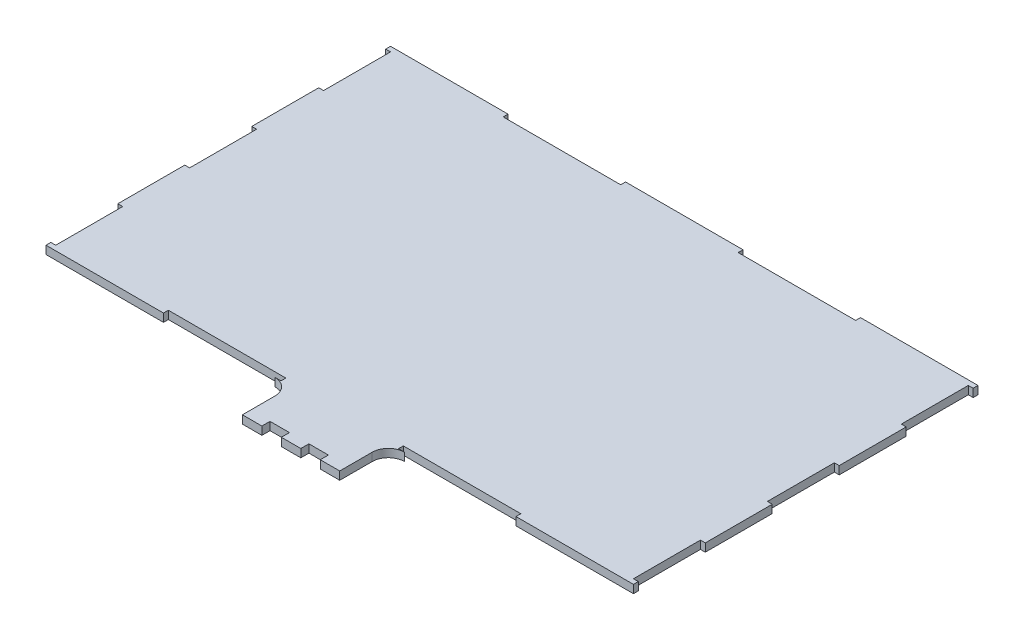
SolidWorks part; units mm, degrees
ref_plane "Front Plane" through (0, 0, 0) normal (0, 0, 1) x (1, 0, 0)
ref_plane "Top Plane" through (0, 0, 0) normal (0, 1, 0) x (1, 0, 0)
ref_plane "Right Plane" through (0, 0, 0) normal (1, 0, 0) x (0, 0, -1)
sketch "Sketch1" plane through (0, 0, 0) normal (0, 1, 0) x (1, 0, 0)
  line L0 (-30, -136.2503) -> (-18, -136.2503)
  line L5 (-181.15, 106.25) -> (181.15, -106.25) construction
  line L6 (-181.15, -106.25) -> (181.15, 106.25) construction
  line L13 (-30, -116.25) -> (-30, -136.2503)
  line L17 (30, -136.2503) -> (30, -116.25)
  line L18 (-18, -131.2503) -> (-6, -131.2503)
  line L20 (18, -136.2503) -> (30, -136.2503)
  line L21 (-6, -136.2503) -> (6, -136.2503)
  line L23 (-18, -136.2503) -> (-18, -131.2503)
  line L24 (-6, -136.2503) -> (-6, -131.2503)
  line L25 (6, -136.2503) -> (6, -131.2503)
  line L26 (18, -136.2503) -> (18, -131.2503)
  line L28 (6, -131.2503) -> (18, -131.2503)
  line L54 (-181.15, 106.25) -> (-181.15, 103.25) construction
  line L55 (181.15, 106.25) -> (108.69, 106.25)
  line L60 (-181.15, -106.25) -> (-181.15, -103.25)
  line L62 (-181.15, 103.25) -> (181.15, 103.25) construction
  line L63 (-108.69, 103.2497) -> (-36.23, 103.2497)
  line L64 (36.23, 106.25) -> (-36.23, 106.25)
  line L65 (36.23, 103.2497) -> (108.69, 103.2497)
  line L66 (-108.69, 103.2497) -> (-108.69, 106.25)
  line L67 (-36.23, 103.2497) -> (-36.23, 106.25)
  line L68 (36.23, 103.2497) -> (36.23, 106.25)
  line L69 (108.69, 103.2497) -> (108.69, 106.25)
  line L70 (-108.69, 106.25) -> (-181.15, 106.25)
  line L71 (-181.15, -103.25) -> (-178.15, -103.25)
  line L72 (-181.15, -103.25) -> (181.15, -103.25) construction
  line L73 (-178.15, -103.25) -> (-178.15, -61.95)
  line L74 (-181.15, -61.95) -> (-181.15, -20.65)
  line L75 (-178.15, -20.65) -> (-178.15, 20.65)
  line L76 (-181.15, 20.65) -> (-181.15, 61.95)
  line L77 (-178.15, 61.95) -> (-178.15, 103.25)
  line L78 (-178.15, 61.95) -> (-181.15, 61.95)
  line L79 (-178.15, 20.65) -> (-181.15, 20.65)
  line L80 (-178.15, -20.65) -> (-181.15, -20.65)
  line L81 (-178.15, -61.95) -> (-181.15, -61.95)
  line L82 (-181.15, 103.25) -> (-181.15, 106.25)
  line L83 (-181.15, 103.25) -> (-178.15, 103.25)
  line L84 (-36.23, -106.25) -> (-40, -106.25)
  line L85 (181.15, -103.25) -> (178.15, -103.25)
  line L86 (178.15, -103.25) -> (178.15, -61.95)
  line L87 (178.15, -61.95) -> (181.15, -61.95)
  line L88 (181.15, -61.95) -> (181.15, -20.65)
  line L89 (178.15, -20.65) -> (181.15, -20.65)
  line L90 (178.15, -20.65) -> (178.15, 20.65)
  line L91 (178.15, 20.65) -> (181.15, 20.65)
  line L92 (181.15, 20.65) -> (181.15, 61.95)
  line L93 (178.15, 61.95) -> (181.15, 61.95)
  line L94 (178.15, 61.95) -> (178.15, 103.25)
  line L95 (181.15, 103.25) -> (178.15, 103.25)
  line L96 (181.15, -106.25) -> (181.15, -103.25)
  line L97 (181.15, 103.25) -> (181.15, 106.25)
  line L98 (-181.15, -106.25) -> (-108.69, -106.25)
  line L99 (108.69, -103.2497) -> (108.69, -106.25)
  line L100 (36.23, -103.2497) -> (108.69, -103.2497)
  line L101 (36.23, -103.2497) -> (36.23, -106.25)
  line L102 (40, -106.25) -> (36.23, -106.25)
  line L103 (-36.23, -103.2497) -> (-36.23, -106.25)
  line L104 (-108.69, -103.2497) -> (-36.23, -103.2497)
  line L105 (-108.69, -103.2497) -> (-108.69, -106.25)
  line L106 (108.69, -106.25) -> (181.15, -106.25)
  arc A0 (-40, -106.25) -> (-30, -116.25) centre (-40, -116.25) cw
  arc A1 (40, -106.25) -> (30, -116.25) centre (40, -116.25) ccw
  point P0 (0, 0)
  dimension "D3" = 10
  dimension "D4" = 10
  dimension "D1" = 212.5
extrude "Boss-Extrude1" add sketch "Sketch1" along normal blind 5
